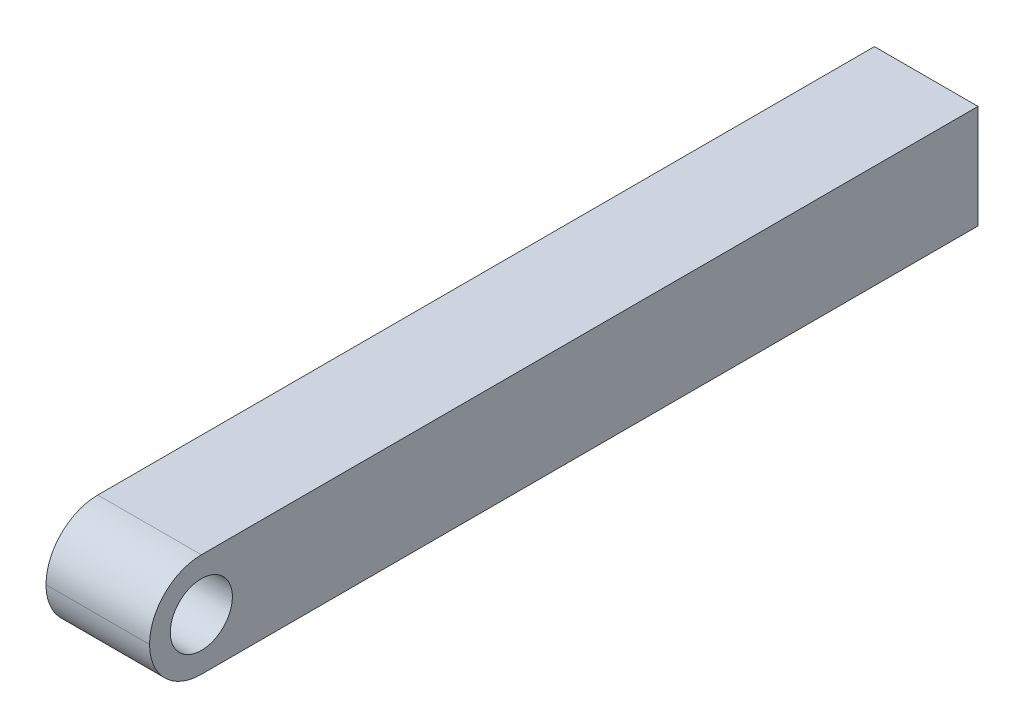
SolidWorks part; units mm, degrees
ref_plane "Front" through (0, 0, 0) normal (0, 0, 1) x (1, 0, 0)
ref_plane "Top" through (0, 0, 0) normal (0, 1, 0) x (1, 0, 0)
ref_plane "Right" through (0, 0, 0) normal (1, 0, 0) x (0, 0, -1)
sketch "Sketch1" plane through (0, 0, 0) normal (0, 0, 1) x (1, 0, 0)
  line L1 (0, 0) -> (-2.54, 0)
  line L2 (0, 0) -> (0, 2.54)
  line L3 (0, 2.54) -> (-2.54, 2.54)
  line L4 (-2.54, 0) -> (-2.54, 2.54)
  dimension "D1" = 2.54
extrude "Boss-Extrude1" add sketch "Sketch1" along normal blind 20.32
sketch "Sketch2" plane through (0, 0, 0) normal (1, 0, 0) x (0, 0, -1)
  line L0 (-20.32, 0) -> (0, 0) construction
  line L1 (-20.32, 0) -> (-20.32, 2.54) construction
  circle A0 centre (-19.05, 1.27) radius 0.762
  dimension "D1" = 1.524
  dimension "D2" = 1.27
  dimension "D3" = 1.27
fillet "Fillet1" radius 1.27 2 edges at (-1.27, 0, 20.32) (-1.27, 2.54, 20.32)
extrude "Cut-Extrude1" cut sketch "Sketch2" against normal through all
